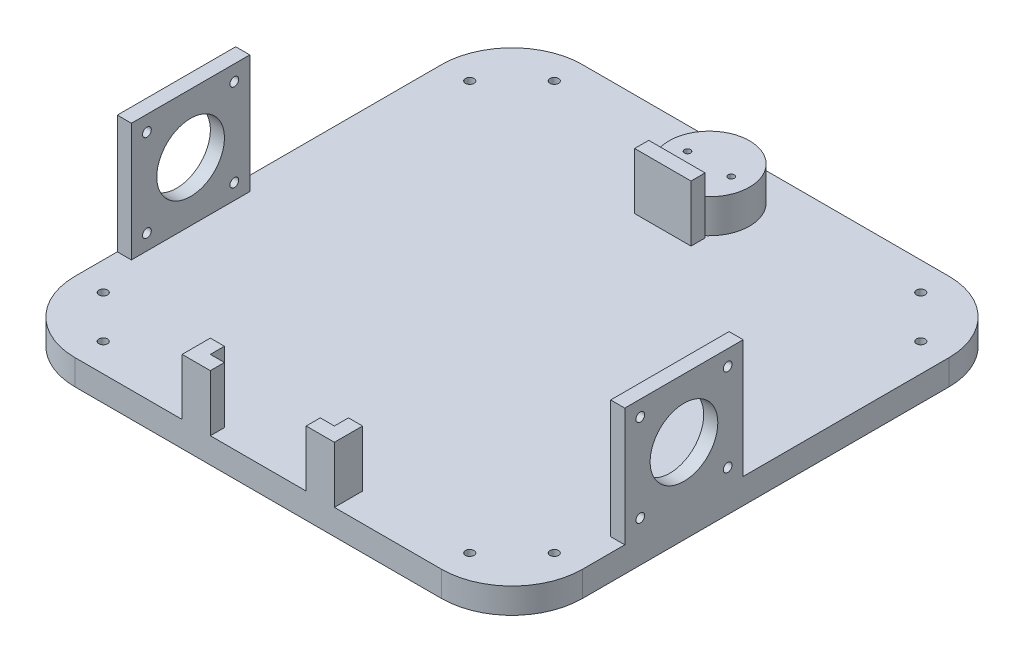
SolidWorks part; units mm, degrees
ref_plane "Front Plane" through (0, 0, 0) normal (0, 0, 1) x (1, 0, 0)
ref_plane "Top Plane" through (0, 0, 0) normal (0, 1, 0) x (1, 0, 0)
ref_plane "Right Plane" through (0, 0, 0) normal (1, 0, 0) x (0, 0, -1)
sketch "Sketch1" plane through (0, 0, 0) normal (0, 1, 0) x (1, 0, 0)
  line L1 (-65, -90) -> (65, -90)
  line L2 (-90, -65) -> (-90, 65)
  line L3 (-65, 90) -> (65, 90)
  line L4 (90, -65) -> (90, 65)
  arc A0 (-90, 65) -> (-65, 90) centre (-65, 65) cw
  arc A1 (65, 90) -> (90, 65) centre (65, 65) cw
  arc A2 (90, -65) -> (65, -90) centre (65, -65) cw
  arc A3 (-65, -90) -> (-90, -65) centre (-65, -65) cw
  point P4 (-90, 0)
  point P6 (0, 90)
  dimension "D3" = 25
  dimension "D1" = 180
  dimension "D2" = 180
extrude "Plate" add sketch "Sketch1" along normal blind 9
sketch "Sketch3" plane through (0, 9, 0) normal (0, 1, 0) x (1, 0, 0)
  line L0 (-65, 90) -> (-65, -90) construction
  line L1 (65, 90) -> (65, -90) construction
  line L2 (-90, 65) -> (90, 65) construction
  line L3 (-90, -65) -> (90, -65) construction
  circle A0 centre (-65, 80) radius 1.525
  circle A1 centre (-80, 65) radius 1.525
  circle A2 centre (80, 65) radius 1.525
  circle A3 centre (80, -65) radius 1.525
  circle A4 centre (65, 80) radius 1.525
  circle A5 centre (65, -80) radius 1.525
  circle A6 centre (-65, -80) radius 1.525
  circle A7 centre (-80, -65) radius 1.525
  dimension "D1" = 3.05
  dimension "D2" = 15
  dimension "D3" = 15
  dimension "D4" = 15
  dimension "D5" = 15
  dimension "D6" = 15
  dimension "D7" = 15
  dimension "D8" = 15
  dimension "D9" = 15
extrude "Hex Holes" cut sketch "Sketch3" against normal through all
sketch "Sketch4" plane through (0, 9, 0) normal (0, 1, 0) x (1, 0, 0)
  line L0 (-22, -85) -> (-17, -85)
  line L1 (-17, -85) -> (-17, -90)
  line L2 (-17, -90) -> (-27, -90)
  line L3 (-27, -90) -> (-27, -80)
  line L4 (-27, -80) -> (-22, -80)
  line L5 (-22, -80) -> (-22, -85)
  line L6 (17, -85) -> (22, -85)
  line L7 (22, -85) -> (22, -80)
  line L8 (22, -80) -> (27, -80)
  line L9 (27, -80) -> (27, -90)
  line L10 (27, -90) -> (17, -90)
  line L11 (17, -90) -> (17, -85)
  line L12 (-90, -65) -> (-90, 65) construction
  line L13 (-65, -90) -> (65, -90) construction
  line L14 (-65, 90) -> (65, 90) construction
  line L15 (-10, 53.5) -> (10, 53.5)
  line L16 (-10, 53.5) -> (-10, 58.5)
  line L17 (-10, 58.5) -> (10, 58.5)
  line L18 (10, 53.5) -> (10, 58.5)
  point P20 (0, 58.5)
  point P23 (0, 90)
  dimension "D1" = 44
  dimension "D2" = 5
  dimension "D3" = 63
  dimension "D4" = 0
  dimension "D5" = 138.5
  dimension "D6" = 5
  dimension "D7" = 20
extrude "Battery Holder" add sketch "Sketch4" along normal blind 20
sketch "Sketch5" plane through (-90, 0, 0) normal (-1, 0, 0) x (0, 0, 1)
  line L0 (-65, 9) -> (65, 9) construction
  line L1 (50, 9) -> (8, 9)
  line L2 (50, 9) -> (50, 51)
  line L3 (50, 51) -> (8, 51)
  line L4 (8, 9) -> (8, 51)
  line L5 (65, 9) -> (65, 0) construction
  circle A0 centre (29, 30) radius 12
  circle A1 centre (13.5, 45.5) radius 1.55
  circle A2 centre (44.5, 45.5) radius 1.55
  circle A3 centre (44.5, 14.5) radius 1.55
  circle A4 centre (13.5, 14.5) radius 1.55
  point P11 (29, 51)
  point P20 (8, 30)
  dimension "D4" = 24
  dimension "D5" = 3.1
  dimension "D1" = 42
  dimension "D2" = 42
  dimension "D3" = 15
  dimension "D6" = 5.5
  dimension "D7" = 5.5
  dimension "D8" = 5.5
  dimension "D9" = 5.5
extrude "Boss-Extrude2" add sketch "Sketch5" against normal blind 5
sketch "Sketch6" plane through (90, 0, 0) normal (1, 0, 0) x (0, 0, -1)
  line L0 (-8, 9) -> (-50, 9)
  line L1 (-8, 9) -> (-8, 51)
  line L2 (-8, 51) -> (-50, 51)
  line L3 (-50, 9) -> (-50, 51)
  line L4 (-65, 9) -> (-65, 0) construction
  line L5 (-65, 9) -> (65, 9) construction
  circle A0 centre (-29, 30) radius 12
  circle A1 centre (-44.5, 45.5) radius 1.55
  circle A2 centre (-13.5, 45.5) radius 1.55
  circle A3 centre (-13.5, 14.5) radius 1.55
  circle A4 centre (-44.5, 14.5) radius 1.55
  point P7 (-29, 51)
  point P15 (-50, 30)
  dimension "D6" = 3.1
  dimension "D7" = 24
  dimension "D1" = 15
  dimension "D2" = 42
  dimension "D3" = 42
  dimension "D4" = 5.5
  dimension "D5" = 5.5
  dimension "D8" = 5.5
  dimension "D9" = 5.5
extrude "Boss-Extrude3" add sketch "Sketch6" against normal blind 5
sketch "Sketch8" plane through (0, 9, 0) normal (0, 1, 0) x (1, 0, 0)
  line L0 (-65, 90) -> (65, 90) construction
  line L1 (0, 90) -> (0, -90) construction
  line L2 (-65, -90) -> (65, -90) construction
  circle A0 centre (0, 70) radius 14.25
  dimension "D2" = 28.5
  dimension "D1" = 20
extrude "Boss-Extrude4" add sketch "Sketch8" along normal blind 12
sketch "Sketch7" plane through (0, 0, 0) normal (0, -1, 0) x (1, 0, 0)
  line L0 (-65, -90) -> (65, -90) construction
  line L1 (0, 90) -> (0, -90) construction
  line L2 (-65, 90) -> (65, 90) construction
  circle A0 centre (0, -70) radius 11.75
  dimension "D2" = 23.5
  dimension "D1" = 20
extrude "Cut-Extrude1" cut sketch "Sketch7" against normal blind 10.6
sketch "Sketch2" plane through (0, 9, 0) normal (0, 1, 0) x (1, 0, 0)
  line L0 (-7.747, 70) -> (7.747, 70) construction
  line L1 (0, 90) -> (0, 70) construction
  line L2 (-65, 90) -> (65, 90) construction
  circle A1 centre (-7.747, 70) radius 1.09
  circle A2 centre (7.747, 70) radius 1.09
  dimension "D3" = 2.18
  dimension "D1" = 15.494
  dimension "D2" = 20
extrude "Caster Holes" cut sketch "Sketch2" against normal through all both and the other way through all
